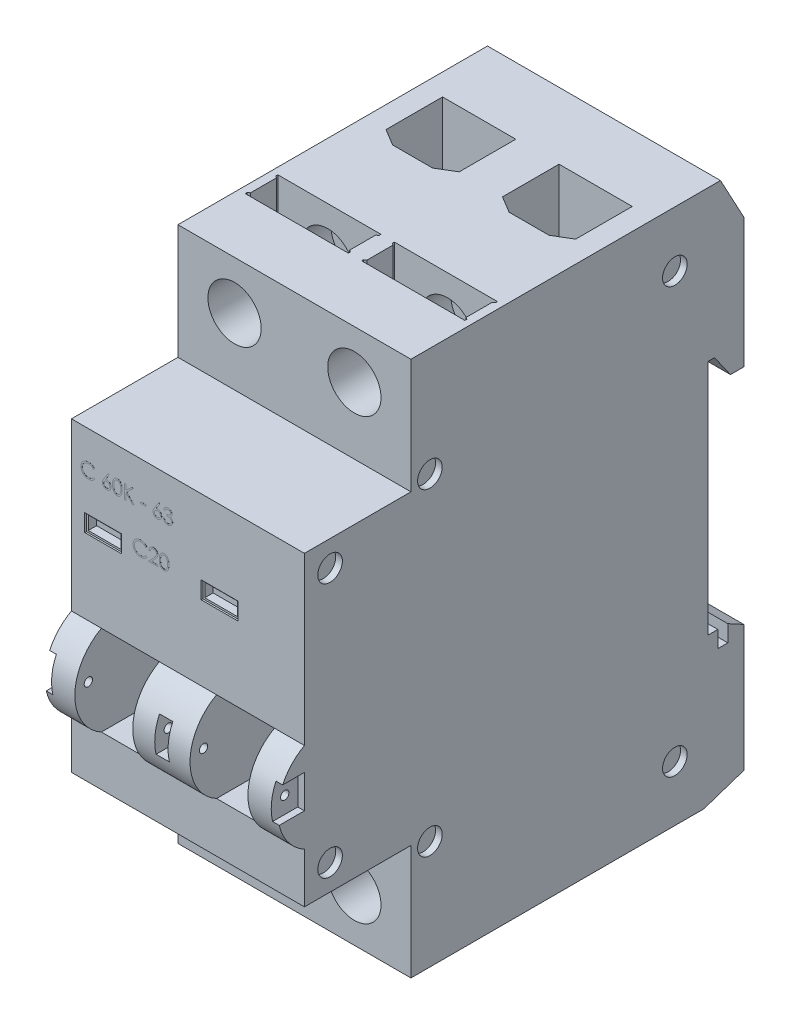
SolidWorks part; units mm, degrees
ref_plane "Alzado" through (0, 0, 0) normal (0, 0, 1) x (1, 0, 0)
ref_plane "Planta" through (0, 0, 0) normal (0, 1, 0) x (1, 0, 0)
ref_plane "Vista lateral" through (0, 0, 0) normal (1, 0, 0) x (0, 0, -1)
sketch "Croquis1" plane through (0, 0, 0) normal (1, 0, 0) x (0, 0, -1)
  line L0 (-33, 23) -> (-17, 23)
  line L1 (-17, 40.25) -> (29.5, 40.25)
  line L2 (-33, 23) -> (-33, -2)
  line L3 (-17, -40.25) -> (27, -40.25)
  line L4 (33, 33.75) -> (33, 14.25)
  line L5 (-33, 40.25) -> (33, -40.25) construction
  line L6 (-33, -40.25) -> (33, 40.25) construction
  line L7 (-33, -23) -> (-17, -23)
  line L8 (-17, 23) -> (-17, 40.25)
  line L9 (-17, -23) -> (-17, -40.25)
  line L10 (29.5, 40.25) -> (33, 33.75)
  line L11 (33, 14.25) -> (31, 14.25)
  line L12 (31, 14.25) -> (28.6, 17.65)
  line L13 (28.6, 17.65) -> (27.6, 17.65)
  line L14 (27.6, 17.65) -> (27.6, -17.95)
  line L15 (27.6, -17.95) -> (29.1, -17.95)
  line L16 (29.1, -17.95) -> (29.1, -20.45)
  line L17 (29.1, -20.45) -> (30.6, -20.45)
  line L18 (30.6, -20.45) -> (30.6, -17.95)
  line L19 (27, -40.25) -> (33, -38.25)
  line L20 (30.6, -17.95) -> (33, -19.25)
  line L21 (-19.3156, -2) -> (-33, -2) construction
  line L22 (-19.3156, -15.5) -> (-33, -15.5) construction
  line L23 (-19.3156, -2) -> (-19.3156, -15.5) construction
  line L24 (-19.3156, -8.75) -> (-37, -8.75) construction
  line L25 (-33, -15.5) -> (-33, -23)
  line L26 (33, -19.25) -> (33, -38.25)
  arc A0 (-33, -2) -> (-33, -15.5) centre (-29.2818, -8.75) ccw
  point P0 (0, 0)
  dimension "D1" = 66
  dimension "D2" = 80.5
  dimension "D3" = 16
  dimension "D4" = 46
  dimension "D5" = 17.25
  dimension "D6" = 46.5
  dimension "D7" = 6.5
  dimension "D8" = 19.5
  dimension "D9" = 64
  dimension "D10" = 1
  dimension "D11" = 60.6
  dimension "D12" = 22.6
  dimension "D13" = 35.6
  dimension "D14" = 1.5
  dimension "D15" = 2.5
  dimension "D16" = 1.5
  dimension "D17" = 44
  dimension "D18" = 16
  dimension "D19" = 2
  dimension "D20" = 19
  dimension "D23" = 4
extrude "Saliente-Extruir1" add sketch "Croquis1" along normal blind 17.5 and the other way blind 17.5
sketch "Croquis2" plane through (17.5, 0, 0) normal (1, 0, 0) x (0, 0, -1)
  line L0 (0, 0) -> (37.946, 0) construction
  line L1 (-17, 40.25) -> (-17, 23) construction
  line L2 (29.5, 40.25) -> (-17, 40.25) construction
  line L3 (-33, 23) -> (-33, -2) construction
  line L4 (-17, 23) -> (-33, 23) construction
  line L5 (33, 14.25) -> (33, 33.75) construction
  circle A0 centre (-14.15, 23.9) radius 1.85
  circle A1 centre (22.65, 31.9) radius 1.85
  circle A2 centre (-29.15, 19.15) radius 1.85
  circle A3 centre (22.65, -31.9) radius 1.85
  circle A4 centre (-14.15, -23.9) radius 1.85
  circle A5 centre (-29.15, -19.15) radius 1.85
  dimension "D1" = 3.7
  dimension "D2" = 3.7
  dimension "D3" = 3.7
  dimension "D4" = 2.85
  dimension "D5" = 16.35
  dimension "D6" = 3.85
  dimension "D7" = 3.85
  dimension "D8" = 8.35
  dimension "D9" = 10.35
extrude "Cortar-Extruir1" cut sketch "Croquis2" against normal blind 1
mirror "Simetría1" about plane through (0, 0, 0) normal (1, 0, 0) of "Cortar-Extruir1"
sketch "Croquis3" plane through (0, 40.25, 0) normal (0, 1, 0) x (1, 0, 0)
  line L0 (0, -17) -> (0, 34.3983) construction
  line L1 (-17.5, -17) -> (17.5, -17) construction
  line L2 (-17.5, 29.5) -> (17.5, 29.5) construction
  line L3 (1, -3) -> (16.5, -3)
  line L4 (1, -3) -> (1, -3.3)
  line L5 (1, -7.9) -> (16.5, -7.9)
  line L6 (16.5, -3) -> (16.5, -3.3)
  line L7 (1, -3) -> (16.5, -7.9) construction
  line L8 (1, -7.9) -> (16.5, -3) construction
  line L9 (3.25, 19.5) -> (14.25, 19.5)
  line L10 (3.25, 19.5) -> (3.25, 11)
  line L11 (5.75, 9.5) -> (11.75, 9.5)
  line L12 (14.25, 19.5) -> (14.25, 11)
  line L13 (3.25, 19.5) -> (14.25, 9.5) construction
  line L14 (3.25, 9.5) -> (14.25, 19.5) construction
  line L15 (0, -17) -> (17.5, -17) construction
  line L16 (8.75, -17) -> (8.75, 30.905) construction
  line L17 (-3.25, 19.5) -> (-3.25, 11)
  line L18 (1, -3.3) -> (1.3, -3.5)
  line L19 (1.3, -3.5) -> (1.3, -7.4)
  line L20 (8.75, -5.45) -> (14.9219, -5.45) construction
  line L21 (1, -7.6) -> (1.3, -7.4)
  line L22 (16.5, -7.6) -> (16.2, -7.4)
  line L23 (16.2, -3.5) -> (16.2, -7.4)
  line L24 (16.5, -3.3) -> (16.2, -3.5)
  line L25 (1, -7.6) -> (1, -7.9)
  line L26 (16.5, -7.6) -> (16.5, -7.9)
  line L27 (-1, -3) -> (-1, -3.3)
  line L28 (-1, -3.3) -> (-1.3, -3.5)
  line L29 (-1.3, -3.5) -> (-1.3, -7.4)
  line L30 (-1, -7.6) -> (-1.3, -7.4)
  line L31 (-1, -7.6) -> (-1, -7.9)
  line L32 (-1, -7.9) -> (-16.5, -7.9)
  line L33 (-16.5, -7.6) -> (-16.5, -7.9)
  line L34 (-16.5, -7.6) -> (-16.2, -7.4)
  line L35 (-16.2, -3.5) -> (-16.2, -7.4)
  line L36 (-16.5, -3.3) -> (-16.2, -3.5)
  line L37 (-16.5, -3) -> (-16.5, -3.3)
  line L38 (-1, -3) -> (-16.5, -3)
  line L39 (11.75, 9.5) -> (14.25, 11)
  line L40 (5.75, 9.5) -> (3.25, 11)
  line L41 (-5.75, 9.5) -> (-3.25, 11)
  line L42 (-5.75, 9.5) -> (-11.75, 9.5)
  line L43 (-11.75, 9.5) -> (-14.25, 11)
  line L44 (-14.25, 19.5) -> (-14.25, 11)
  line L45 (-3.25, 19.5) -> (-14.25, 19.5)
  point P5 (8.75, -5.45)
  point P10 (8.75, 14.5)
  dimension "D1" = 4.9
  dimension "D2" = 15.5
  dimension "D3" = 0.3
  dimension "D4" = 0.3
  dimension "D5" = 0.5
  dimension "D6" = 10
  dimension "D7" = 11
  dimension "D9" = 1.5
  dimension "D10" = 12.5
  dimension "D11" = 32.5
extrude "Cortar-Extruir2" cut sketch "Croquis3" against normal blind 12.5
mirror "Simetría2" about plane through (0, 0, 0) normal (0, 1, 0) of "Cortar-Extruir2"
sketch "Croquis4" plane through (0, 0, 17) normal (0, 0, 1) x (1, 0, 0)
  line L0 (0, 40.25) -> (0, 25.9217) construction
  line L1 (-17.5, 40.25) -> (17.5, 40.25) construction
  line L3 (-17.5, 23) -> (17.5, 23) construction
  circle A0 centre (9, 33) radius 4
  circle A1 centre (-9, 33) radius 4
  dimension "D1" = 8
  dimension "D2" = 9
  dimension "D3" = 10
extrude "Cortar-Extruir3" cut sketch "Croquis4" against normal blind 18.5
mirror "Simetría3" about plane through (0, 0, 0) normal (0, 1, 0) of "Cortar-Extruir3"
sketch "Croquis5" plane through (0, 0, 33) normal (0, 0, 1) x (1, 0, 0)
  line L0 (0, 23) -> (0, -5.1647) construction
  line L1 (-17.5, 23) -> (17.5, 23) construction
  line L2 (-17.5, 23) -> (-17.5, -2) construction
  line L3 (-15.5, 11.8) -> (-10, 11.8)
  line L4 (-15.5, 11.8) -> (-15.5, 9.2)
  line L5 (-15.5, 9.2) -> (-10, 9.2)
  line L6 (-10, 11.8) -> (-10, 9.2)
  line L7 (-15.5, 11.8) -> (-10, 9.2) construction
  line L8 (-15.5, 9.2) -> (-10, 11.8) construction
  line L9 (-17.5, -2) -> (17.5, -2) construction
  line L11 (2, 11.8) -> (7.5, 11.8)
  line L12 (2, 11.8) -> (2, 9.2)
  line L13 (2, 9.2) -> (7.5, 9.2)
  line L14 (7.5, 11.8) -> (7.5, 9.2)
  line L15 (2, 11.8) -> (7.5, 9.2) construction
  line L16 (2, 9.2) -> (7.5, 11.8) construction
  point P5 (-12.75, 10.5)
  point P14 (4.75, 10.5)
  dimension "D1" = 5.5
  dimension "D2" = 2.6
  dimension "D3" = 2
  dimension "D4" = 11.2
  dimension "D5" = 5.5
  dimension "D6" = 2
extrude "Cortar-Extruir4" cut sketch "Croquis5" against normal blind 0.25
sketch "Croquis6" plane through (0, 0, 32.75) normal (0, 0, 1) x (1, 0, 0)
  line L1 (-15.2201, 11.5158) -> (-10.2799, 11.5158)
  line L2 (-15.2201, 11.5158) -> (-15.2201, 9.4842)
  line L3 (-15.2201, 9.4842) -> (-10.2799, 9.4842)
  line L4 (-10.2799, 11.5158) -> (-10.2799, 9.4842)
  line L5 (-15.2201, 11.5158) -> (-10.2799, 9.4842) construction
  line L6 (-15.2201, 9.4842) -> (-10.2799, 11.5158) construction
  line L7 (2.28, 11.5158) -> (7.22, 11.5158)
  line L8 (2.28, 11.5158) -> (2.28, 9.4842)
  line L9 (2.28, 9.4842) -> (7.22, 9.4842)
  line L10 (7.22, 11.5158) -> (7.22, 9.4842)
  line L11 (2.28, 11.5158) -> (7.22, 9.4842) construction
  line L12 (2.28, 9.4842) -> (7.22, 11.5158) construction
  line L13 (7.5, 9.2) -> (7.5, 11.8) construction
  line L14 (2, 11.8) -> (2, 9.2) construction
  point P0 (-12.75, 10.5)
  point P5 (4.75, 10.5)
  dimension "D1" = 0.28
  dimension "D2" = 0.28
extrude "Cortar-Extruir5" cut sketch "Croquis6" against normal blind 1.25
ref_plane "Plano1" through (0, 0, 33) normal (0, 0, 1) x (1, 0, 0)
sketch "Croquis7" plane through (0, 0, 33) normal (0, 0, 1) x (1, 0, 0)
  line L0 (0, -2) -> (0, -20.2897) construction
  line L1 (-17.5, -2) -> (17.5, -2) construction
  line L2 (17.5, -15.5) -> (17.5, -2) construction
  line L3 (4.3, -2) -> (13, -2)
  line L4 (4.3, -2) -> (4.3, -15.5)
  line L5 (4.3, -15.5) -> (13, -15.5)
  line L6 (13, -2) -> (13, -15.5)
  line L7 (4.3, -2) -> (13, -15.5) construction
  line L8 (4.3, -15.5) -> (13, -2) construction
  line L9 (-17.5, -15.5) -> (17.5, -15.5) construction
  line L10 (-4.3, -2) -> (-13, -2)
  line L11 (-13, -2) -> (-13, -15.5)
  line L12 (-4.3, -15.5) -> (-13, -15.5)
  line L13 (-4.3, -2) -> (-4.3, -15.5)
  point P5 (8.65, -8.75)
  dimension "D1" = 8.7
  dimension "D2" = 4.5
extrude "Cortar-Extruir6" cut sketch "Croquis7" along normal blind 10.25 and the other way blind 13.25
sketch "Croquis8" plane through (0, -40.25, 0) normal (0, -1, 0) x (1, 0, 0)
  line L0 (0, -27) -> (0, -4.3778) construction
  line L1 (-17.5, -27) -> (17.5, -27) construction
  line L2 (8.75, -19.5) -> (8.75, -27.9198) construction
  line L3 (4.75, -23) -> (12.75, -23)
  line L4 (4.75, -23) -> (4.75, -25)
  line L5 (4.75, -25) -> (12.75, -25)
  line L6 (12.75, -23) -> (12.75, -25)
  line L7 (4.75, -23) -> (12.75, -25) construction
  line L8 (4.75, -25) -> (12.75, -23) construction
  line L9 (14.25, -19.5) -> (3.25, -19.5) construction
  line L10 (-4.75, -25) -> (-12.75, -25)
  line L11 (-12.75, -23) -> (-12.75, -25)
  line L12 (-4.75, -23) -> (-12.75, -23)
  line L13 (-4.75, -23) -> (-4.75, -25)
  point P5 (8.75, -24)
  dimension "D1" = 2
  dimension "D2" = 8
  dimension "D3" = 2
extrude "Cortar-Extruir7" cut sketch "Croquis8" against normal blind 5
sketch "Croquis10" plane through (0, 0, -33) normal (0, 0, -1) x (-1, 0, 0)
  line L0 (0, -19.25) -> (0, -40.9421) construction
  line L1 (17.5, -19.25) -> (-17.5, -19.25) construction
  line L2 (13.5, -19.25) -> (13.5, -32.25)
  line L3 (13.5, -32.25) -> (10.3, -32.25)
  line L4 (10.3, -32.25) -> (10.3, -38.25)
  line L5 (17.5, -38.25) -> (-17.5, -38.25) construction
  line L6 (7.3, -38.25) -> (7.3, -26.25)
  line L7 (17.5, -38.25) -> (17.5, -19.25) construction
  line L8 (0, -19.25) -> (17.5, -19.25)
  line L9 (8.75, -19.25) -> (8.75, -38.25) construction
  line L10 (7.2, -32.25) -> (7.2, -38.25)
  line L11 (4, -32.25) -> (7.2, -32.25)
  line L12 (4, -19.25) -> (4, -32.25)
  line L13 (10.2, -38.25) -> (10.2, -26.25)
  line L14 (10.2, -26.25) -> (11.2, -26.25)
  line L15 (11.2, -26.25) -> (11.2, -22.75)
  line L16 (11.2, -22.75) -> (13.4415, -22.1089)
  line L17 (13.4415, -22.1089) -> (13.4415, -19.25)
  line L18 (7.3, -26.25) -> (6.3, -26.25)
  line L19 (6.3, -26.25) -> (6.3, -22.75)
  line L20 (6.3, -22.75) -> (4.0585, -22.1089)
  line L21 (4.0585, -22.1089) -> (4.0585, -19.25)
  line L22 (7.3, -38.25) -> (10.2, -38.25)
  line L23 (10.3, -38.25) -> (10.2, -38.25)
  line L24 (7.2, -38.25) -> (7.3, -38.25)
  line L25 (0, -19.25) -> (-17.5, -19.25)
  line L26 (-10.3, -38.25) -> (-10.2, -38.25)
  line L27 (-7.2, -38.25) -> (-7.3, -38.25)
  line L28 (-7.3, -38.25) -> (-10.2, -38.25)
  line L29 (-10.2, -38.25) -> (-10.2, -26.25)
  line L30 (-13.4415, -22.1089) -> (-13.4415, -19.25)
  line L31 (-13.5, -19.25) -> (-13.5, -32.25)
  line L32 (-11.2, -26.25) -> (-11.2, -22.75)
  line L33 (-11.2, -22.75) -> (-13.4415, -22.1089)
  line L34 (-13.5, -32.25) -> (-10.3, -32.25)
  line L35 (-10.3, -32.25) -> (-10.3, -38.25)
  line L36 (-7.2, -32.25) -> (-7.2, -38.25)
  line L37 (-4, -32.25) -> (-7.2, -32.25)
  line L38 (-7.3, -38.25) -> (-7.3, -26.25)
  line L39 (-7.3, -26.25) -> (-6.3, -26.25)
  line L40 (-6.3, -26.25) -> (-6.3, -22.75)
  line L41 (-4.0585, -22.1089) -> (-4.0585, -19.25)
  line L42 (-4, -19.25) -> (-4, -32.25)
  line L43 (-6.3, -22.75) -> (-4.0585, -22.1089)
  line L44 (-10.2, -26.25) -> (-11.2, -26.25)
  line M23 (17.5, -19.25) -> (-17.5, -19.25)
  line M25 (-17.5, -38.25) -> (17.5, -38.25)
  dimension "D1" = 13
  dimension "D2" = 4
  dimension "D3" = 3.2
  dimension "D4" = 12
  dimension "D5" = 3.5
  dimension "D6" = 0.1
  dimension "D7" = 1
extrude "Cortar-Extruir8" cut sketch "Croquis10" against normal blind 3 contours L29 L44 L32 L33 L30 L25 L31 L34 L35 M25 | L43 L40 L39 L38 L36 L37 L42 L25 L41 M25 | L20 L21 L12 L11 L10 L6 L18 L19 M23 M25 | L17 L16 L15 L14 L13 L4 L3 L2 M25 M23 region at (-11.9863, -27.849, -33) region at (-5.5137, -27.849, -33) region at (5.5137, -27.849, -33) region at (11.9863, -27.849, -33)
fillet "Redondeo1" radius 0.25 4 edges at (6.3, -26.25, -31.5) (11.2, -26.25, -31.5) (-6.3, -26.25, -31.5) (-11.2, -26.25, -31.5)
fillet "Redondeo2" radius 1 4 edges at (6.3, -22.75, -31.5) (-6.3, -22.75, -31.5) (11.2, -22.75, -31.5) (-11.2, -22.75, -31.5)
ref_plane "Plano2" through (0, 0, 36) normal (0, 0, 1) x (1, 0, 0)
sketch "Croquis11" plane through (0, 0, 36) normal (0, 0, 1) x (1, 0, 0)
  line L0 (0, 0) -> (0, -21) construction
  line L1 (-1, -5.5) -> (1, -5.5)
  line L2 (1, -5.5) -> (1, -10.5)
  line L3 (1, -10.5) -> (-1, -10.5)
  line L4 (4.3, -2) -> (4.3, -15.5) construction
  line L5 (-4.3, -15.5) -> (4.3, -15.5) construction
  line L6 (-1, -5.5) -> (-1, -10.5)
  line L7 (0, -5.5) -> (0, -10.5)
  line L8 (-16.5, -5.5) -> (-16.5, -10.5)
  line L10 (16.5, -5.5) -> (16.5, -10.5)
  line L11 (-16.5, -5.5) -> (-17.5, -5.5)
  line L12 (-17.5, -2) -> (-17.5, -15.5) construction
  line L13 (-17.5, -5.5) -> (-17.5, -10.5)
  line L14 (-17.5, -10.5) -> (-16.5, -10.5)
  line L15 (16.5, -5.5) -> (17.5, -5.5)
  line L16 (17.5, -15.5) -> (17.5, -2) construction
  line L17 (17.5, -5.5) -> (17.5, -10.5)
  line L18 (17.5, -10.5) -> (16.5, -10.5)
  point P13 (0, -10.5)
  point P14 (0, -5.5)
  dimension "D1" = 3.3
  dimension "D2" = 5
  dimension "D3" = 5
  dimension "D4" = 2
  dimension "D5" = 2
extrude "Cortar-Extruir9" cut sketch "Croquis11" against normal blind 3 and the other way blind 3 contours L7 L1 L6 L3 | L1 L7 L3 L2 | L18 L17 L15 L10 | L13 L14 L8 L11 region at (-0.5, -8, 36) region at (0.5, -8, 36) region at (17, -8, 36)
sketch "Croquis12" plane through (-16.5, 0, 0) normal (-1, 0, 0) x (0, 0, 1)
  circle A0 centre (34.9571, -8) radius 0.625
  dimension "D1" = 1.25
extrude "Cortar-Extruir10" cut sketch "Croquis12" against normal blind 35
sketch "Croquis13" plane through (0, 0, 33) normal (0, 0, 1) x (1, 0, 0)
  line L0 (-8.3844, 10.2673) -> (-0.2469, 10.2673) construction
  line L1 (-16.2233, 16.4901) -> (6.6119, 16.4901) construction
  text T0 "C 60K - 63" font "Century Gothic" height in points 8
  text T1 "C20" font "Century Gothic" height in points 8
extrude "Saliente-Extruir2" add sketch "Croquis13" along normal blind 0.01 separate body
